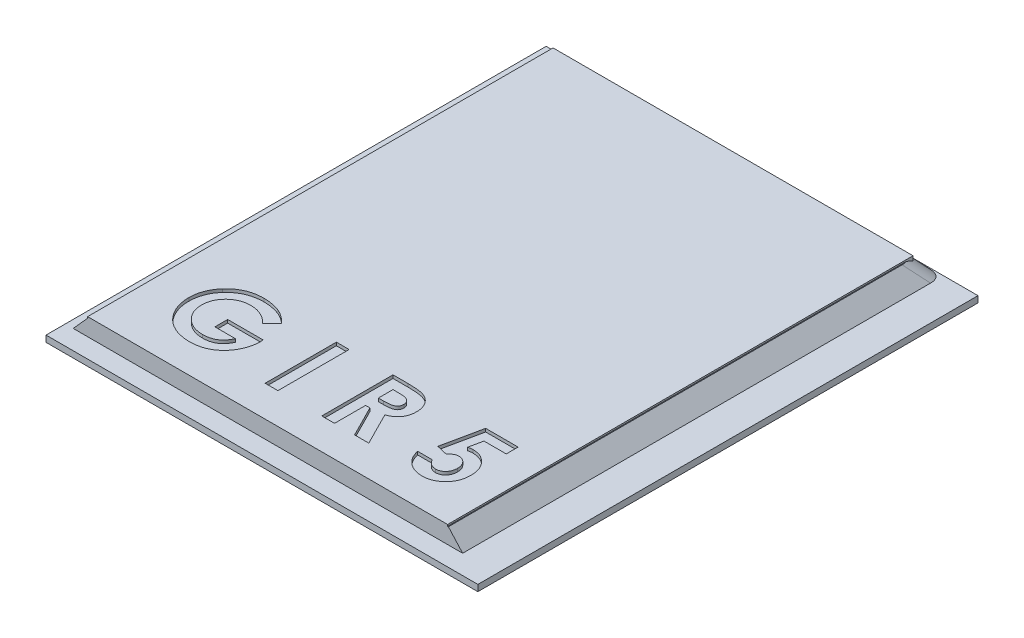
SolidWorks part; units mm, degrees
ref_plane "Спереди" through (0, 0, 0) normal (0, 0, 1) x (1, 0, 0)
ref_plane "Сверху" through (0, 0, 0) normal (0, 1, 0) x (1, 0, 0)
ref_plane "Справа" through (0, 0, 0) normal (1, 0, 0) x (0, 0, -1)
sketch "Эскиз1" plane through (0, 0, 0) normal (0, 0, 1) x (1, 0, 0)
  line L0 (0, 4.8135) -> (17.3785, 4.8135)
  line L1 (17.3785, 4.8135) -> (18.2785, 3.8135)
  line L2 (18.2785, 3.8135) -> (-6.3215, 3.8135)
  line L3 (-6.3215, 3.8135) -> (-5.4215, 4.8135)
  line L4 (-5.4215, 4.8135) -> (0, 4.8135)
  dimension "D1" = 22.8
  dimension "D2" = 1
  dimension "D3" = 0.9
  dimension "D4" = 0.9
extrude "Бобышка-Вытянуть1" add sketch "Эскиз1" along normal blind 29.4 contours L4 L0 L1 L2 L3
sketch "Эскиз3" plane through (0, 4.8135, 0) normal (0, 1, 0) x (1, 0, 0)
  line L0 (-5.4215, 0) -> (17.3785, 0) construction
  line L1 (-5.4115, 0) -> (17.3275, 0)
  line L2 (-5.4115, 0) -> (-5.4115, -29.4)
  line L3 (-5.4115, -29.4) -> (17.3275, -29.4)
  line L4 (17.3275, 0) -> (17.3275, -29.4)
  line L5 (-5.4215, -29.4) -> (17.3785, -29.4) construction
  line L6 (-5.4215, -29.4) -> (-5.4215, 0) construction
  line L7 (17.3785, -29.4) -> (17.3785, 0) construction
  dimension "D1" = 0.01
  dimension "D2" = 0.051
extrude "Бобышка-Вытянуть2" add sketch "Эскиз3" along normal blind 0.1
ref_plane "Плоскость4" through (0, 3.5935, 0) normal (0, -1, 0) x (-1, 0, 0)
sketch "Эскиз5" plane through (0, 3.5935, 0) normal (0, -1, 0) x (-1, 0, 0)
  line L1 (-20.241, 1.1891) -> (7.0374, 1.1891)
  line L2 (-20.241, 1.1891) -> (-20.241, -30.4026)
  line L3 (-20.241, -30.4026) -> (7.0374, -30.4026)
  line L4 (7.0374, 1.1891) -> (7.0374, -30.4026)
extrude "Бобышка-Вытянуть3" add sketch "Эскиз5" along normal blind 0.4 separate body
sketch "Эскиз2" plane through (0, 4.8135, 0) normal (0, 1, 0) x (1, 0, 0)
  line L1 (-0.6388, -4.0743) -> (11.5798, -4.0743)
  line L2 (-0.6388, -4.0743) -> (-0.6388, -19.7023)
  line L3 (-0.6388, -19.7023) -> (11.5798, -19.7023)
  line L4 (11.5798, -4.0743) -> (11.5798, -19.7023)
sketch "Эскиз6" plane through (0, 0, 0) normal (1, 0, 0) x (0, 0, -1)
  line L1 (0, 4.8135) -> (0.9, 3.8093)
  line L2 (0.9, 3.8093) -> (0, 3.8135)
  line L3 (0, 4.8135) -> (0, 3.8135)
  dimension "D1" = 0.9
extrude "Бобышка-Вытянуть4" add sketch "Эскиз6" along normal up to vertex (18.2785 mm away) and the other way up to vertex (6.3215 mm away) up to point (18.2785, 3.8135, 0) other way up to point (-6.3215, 3.8135, 0)
sketch "Эскиз7" plane through (0, 0, 0) normal (0, 0, 1) x (1, 0, 0)
  line L0 (-5.4215, 4.8135) -> (-6.3215, 3.8135)
  line L1 (-6.3215, 3.8135) -> (-6.3215, 4.8135)
  line L2 (-6.3215, 4.8135) -> (-5.4215, 4.8135)
  line L3 (17.3785, 4.8135) -> (18.2785, 4.8135)
  line L4 (18.2785, 4.8135) -> (18.2785, 3.8135)
  line L5 (18.2785, 3.8135) -> (17.3785, 4.8135)
extrude "Вырез-Вытянуть5" cut sketch "Эскиз7" against normal blind 10.4
fillet "Скругление1" radius 1 2 edges at (17.8285, 4.3135, -0.4481) (-5.8715, 4.3135, -0.4481)
sketch "Эскиз8" plane through (0, 4.9135, 0) normal (0, 1, 0) x (1, 0, 0)
  text T0 "<b>G I R 5</b>" font "Century Gothic" height 4.5
  point P1 (-3.545, -27.4391)
extrude "Вырез-Вытянуть6" cut sketch "Эскиз8" against normal blind 0.2
